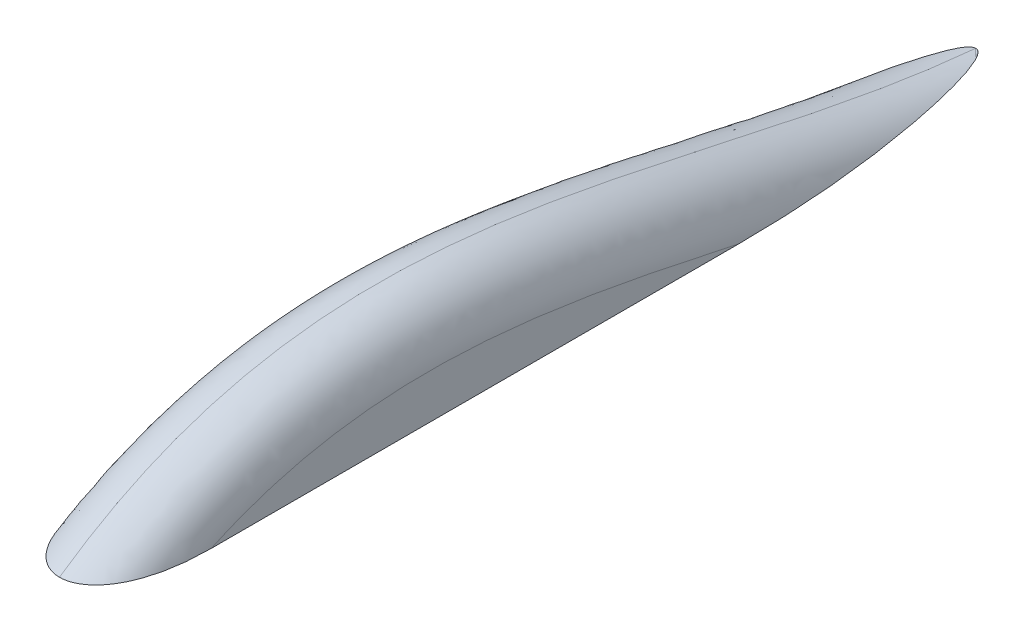
SolidWorks part; units mm, degrees
ref_plane "Front Plane" through (0, 0, 0) normal (0, 0, 1) x (1, 0, 0)
ref_plane "Top Plane" through (0, 0, 0) normal (0, 1, 0) x (1, 0, 0)
ref_plane "Right Plane" through (0, 0, 0) normal (1, 0, 0) x (0, 0, -1)
sketch "Sketch1" plane through (0, 0, 0) normal (1, 0, 0) x (0, 0, -1)
  line L0 (-43.25, 0) -> (46.75, 0)
  spline S0 degree 3 poles (-43.25, 0) (-15.25, 19.7002) (16.8773, 2.6894) (46.75, 0) knots 0 0 0 0 1 1 1 1
  dimension "D1" = 90
extrude "Boss-Extrude1" add sketch "Sketch1" along normal blind 10
fillet "Fillet1" radius 5 2 edges
